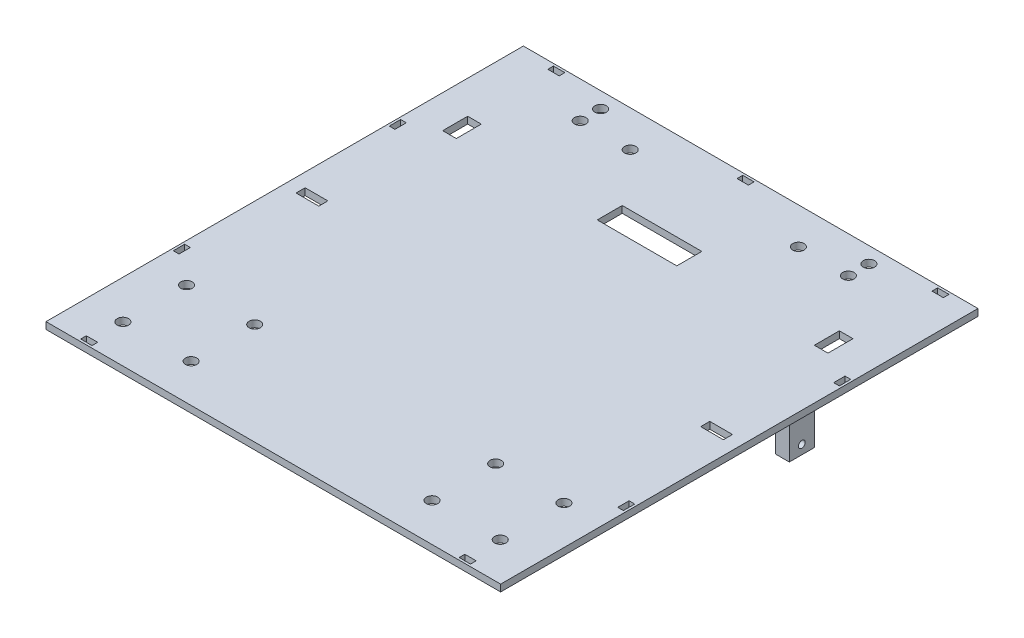
SolidWorks part; units mm, degrees
material "ABS"
ref_plane "Front Plane" through (0, 0, 0) normal (0, 0, 1) x (1, 0, 0)
ref_plane "Top Plane" through (0, 0, 0) normal (0, 1, 0) x (1, 0, 0)
ref_plane "Right Plane" through (0, 0, 0) normal (1, 0, 0) x (0, 0, -1)
sketch "Sketch1" plane through (0, 0, 0) normal (0, 1, 0) x (1, 0, 0)
  line L1 (100, 105) -> (-100, 105)
  line L2 (100, 105) -> (100, -105)
  line L3 (100, -105) -> (-100, -105)
  line L4 (-100, 105) -> (-100, -105)
  line L5 (100, 105) -> (-100, -105) construction
  line L6 (100, -105) -> (-100, 105) construction
  line L11 (94, 3) -> (84, 3)
  line L12 (94, 3) -> (94, -1)
  line L13 (94, -1) -> (84, -1)
  line L14 (84, 3) -> (84, -1)
  line L15 (94, 3) -> (84, -1) construction
  line L16 (94, -1) -> (84, 3) construction
  line L17 (-94, -1) -> (-84, -1)
  line L18 (-94, -1) -> (-94, 3)
  line L19 (-94, 3) -> (-84, 3)
  line L20 (-84, -1) -> (-84, 3)
  line L21 (-94, -1) -> (-84, 3) construction
  line L22 (-94, 3) -> (-84, -1) construction
  line L23 (-85.5, 38) -> (-79.5, 38)
  line L24 (-85.5, 38) -> (-85.5, 49)
  line L25 (-85.5, 49) -> (-79.5, 49)
  line L26 (-79.5, 38) -> (-79.5, 49)
  line L27 (-85.5, 38) -> (-79.5, 49) construction
  line L28 (-85.5, 49) -> (-79.5, 38) construction
  line L29 (78, 38) -> (84, 38)
  line L30 (78, 38) -> (78, 49)
  line L31 (78, 49) -> (84, 49)
  line L32 (84, 38) -> (84, 49)
  line L33 (78, 38) -> (84, 49) construction
  line L34 (78, 49) -> (84, 38) construction
  line L35 (85.75, -104) -> (80.75, -104)
  line L36 (85.75, -104) -> (85.75, -101.5)
  line L37 (85.75, -101.5) -> (80.75, -101.5)
  line L38 (80.75, -104) -> (80.75, -101.5)
  line L39 (85.75, -104) -> (80.75, -101.5) construction
  line L40 (85.75, -101.5) -> (80.75, -104) construction
  line L41 (-2.5, 101.5) -> (2.5, 101.5)
  line L42 (-2.5, 101.5) -> (-2.5, 104)
  line L43 (-2.5, 104) -> (2.5, 104)
  line L44 (2.5, 101.5) -> (2.5, 104)
  line L45 (-2.5, 101.5) -> (2.5, 104) construction
  line L46 (-2.5, 104) -> (2.5, 101.5) construction
  line L47 (-85.75, -104) -> (-80.75, -104)
  line L48 (-85.75, -104) -> (-85.75, -101.5)
  line L49 (-85.75, -101.5) -> (-80.75, -101.5)
  line L50 (-80.75, -104) -> (-80.75, -101.5)
  line L51 (-85.75, -104) -> (-80.75, -101.5) construction
  line L52 (-85.75, -101.5) -> (-80.75, -104) construction
  line L53 (-80.75, 104) -> (-85.75, 104)
  line L54 (-80.75, 104) -> (-80.75, 101.5)
  line L55 (-80.75, 101.5) -> (-85.75, 101.5)
  line L56 (-85.75, 104) -> (-85.75, 101.5)
  line L57 (-80.75, 104) -> (-85.75, 101.5) construction
  line L58 (-80.75, 101.5) -> (-85.75, 104) construction
  line L59 (83.25, 101.5) -> (88.25, 101.5)
  line L60 (83.25, 101.5) -> (83.25, 104)
  line L61 (83.25, 104) -> (88.25, 104)
  line L62 (88.25, 101.5) -> (88.25, 104)
  line L63 (83.25, 101.5) -> (88.25, 104) construction
  line L64 (83.25, 104) -> (88.25, 101.5) construction
  line L65 (99, -45) -> (96.5, -45)
  line L66 (99, -45) -> (99, -50)
  line L67 (99, -50) -> (96.5, -50)
  line L68 (96.5, -45) -> (96.5, -50)
  line L69 (99, -45) -> (96.5, -50) construction
  line L70 (99, -50) -> (96.5, -45) construction
  line L71 (99, 50) -> (96.5, 50)
  line L72 (99, 50) -> (99, 45)
  line L73 (99, 45) -> (96.5, 45)
  line L74 (96.5, 50) -> (96.5, 45)
  line L75 (99, 50) -> (96.5, 45) construction
  line L76 (99, 45) -> (96.5, 50) construction
  line L77 (-99, -45) -> (-96.5, -45)
  line L78 (-99, -45) -> (-99, -50)
  line L79 (-99, -50) -> (-96.5, -50)
  line L80 (-96.5, -45) -> (-96.5, -50)
  line L81 (-99, -45) -> (-96.5, -50) construction
  line L82 (-99, -50) -> (-96.5, -45) construction
  line L83 (-99, 45) -> (-96.5, 45)
  line L84 (-99, 45) -> (-99, 50)
  line L85 (-99, 50) -> (-96.5, 50)
  line L86 (-96.5, 45) -> (-96.5, 50)
  line L87 (-99, 45) -> (-96.5, 50) construction
  line L88 (-99, 50) -> (-96.5, 45) construction
  line L89 (84, 55) -> (78, 55)
  line L90 (84, 55) -> (84, 66)
  line L91 (84, 66) -> (78, 66)
  line L92 (78, 55) -> (78, 66)
  line L93 (-79.5, 55) -> (-85.5, 55)
  line L94 (-79.5, 55) -> (-79.5, 66)
  line L95 (-79.5, 66) -> (-85.5, 66)
  line L96 (-85.5, 55) -> (-85.5, 66)
  line L97 (-17.5, 66) -> (17.5, 66)
  line L98 (-17.5, 66) -> (-17.5, 55)
  line L99 (-17.5, 55) -> (17.5, 55)
  line L100 (17.5, 66) -> (17.5, 55)
  circle A0 centre (-59, 98) radius 2.5
  circle A1 centre (-59, 89) radius 2.5
  circle A2 centre (-37, 89) radius 2.5
  circle A3 centre (59, 98) radius 2.5
  circle A4 centre (59, 89) radius 2.5
  circle A5 centre (37, 89) radius 2.5
  circle A6 centre (83, -88.1753) radius 2.5
  circle A7 centre (83, -60.1753) radius 2.4959
  circle A8 centre (53, -88.1753) radius 2.5
  circle A9 centre (53, -60.1753) radius 2.5
  circle A10 centre (-83, -88.1753) radius 2.5
  circle A11 centre (-53, -88.1753) radius 2.5
  circle A12 centre (-53, -60.1753) radius 2.5
  circle A13 centre (-83, -60.1753) radius 2.5
  point P0 (0, 0)
  point P6 (89, 1)
  point P23 (-89, 1)
  point P28 (-82.5, 43.5)
  point P33 (81, 43.5)
  point P38 (83.25, -102.75)
  point P43 (0, 102.75)
  point P48 (-83.25, -102.75)
  point P53 (-83.25, 102.75)
  point P58 (85.75, 102.75)
  point P59 (97.75, -47.5)
  point P68 (97.75, -45)
  point P69 (97.75, 47.5)
  point P74 (-97.75, -47.5)
  point P79 (-97.75, 47.5)
  dimension "D7" = 16
  dimension "D8" = 63
  dimension "D9" = 16
  dimension "D11" = 7
  dimension "D13" = 41
  dimension "D15" = 63
  dimension "D17" = 10
  dimension "D79" = 28
  dimension "D80" = 30
  dimension "D82" = 28
  dimension "D83" = 30
  dimension "D1" = 200
  dimension "D2" = 210
  dimension "D3" = 41
  dimension "D4" = 41
  dimension "D5" = 7
  dimension "D6" = 104
  dimension "D10" = 16
  dimension "D12" = 16
  dimension "D14" = 41
  dimension "D16" = 6
  dimension "D18" = 4
  dimension "D19" = 104
  dimension "D20" = 6
  dimension "D21" = 4
  dimension "D22" = 10
  dimension "D23" = 56
  dimension "D24" = 14.5
  dimension "D25" = 11
  dimension "D26" = 6
  dimension "D27" = 56
  dimension "D28" = 6
  dimension "D29" = 11
  dimension "D30" = 16
  dimension "D31" = 14.25
  dimension "D32" = 1
  dimension "D33" = 5
  dimension "D34" = 2.5
  dimension "D35" = 1
  dimension "D36" = 100
  dimension "D37" = 5
  dimension "D38" = 2.5
  dimension "D39" = 1
  dimension "D40" = 14.25
  dimension "D41" = 5
  dimension "D42" = 2.5
  dimension "D43" = 14.25
  dimension "D44" = 1
  dimension "D45" = 5
  dimension "D46" = 2.5
  dimension "D47" = 14.25
  dimension "D48" = 1
  dimension "D49" = 5
  dimension "D50" = 2.5
  dimension "D51" = 1
  dimension "D52" = 5
  dimension "D53" = 2.5
  dimension "D54" = 55
  dimension "D55" = 55
  dimension "D56" = 1
  dimension "D57" = 5
  dimension "D58" = 2.5
  dimension "D59" = 1
  dimension "D60" = 55
  dimension "D61" = 2.5
  dimension "D62" = 5
  dimension "D63" = 55
  dimension "D64" = 1
  dimension "D65" = 2.5
  dimension "D66" = 5
  dimension "D67" = 16
  dimension "D68" = 11
  dimension "D69" = 6
  dimension "D70" = 39
  dimension "D71" = 14.5
  dimension "D72" = 39
  dimension "D73" = 11
  dimension "D74" = 6
  dimension "D75" = 39
  dimension "D76" = 82.5
  dimension "D77" = 35
  dimension "D78" = 11
  dimension "D81" = 17
  dimension "D84" = 17
extrude "MainBody" add sketch "Sketch1" along normal blind 1
extrude "SayapRoda" add sketch "Sketch1<4>" against normal blind 30 and the other way blind 3 separate body contours L23 L26 L25 L24 | L29 L32 L31 L30 region at (-82.5, 0, -43.5) region at (81, 0, -43.5)
sketch "Sketch1<4>" plane through (0, 0, 0) normal (0, 1, 0) x (1, 0, 0) same geometry as "Sketch1"
hole_wizard "Hole1" positions "3DSketch2" profile "Sketch9" legacy end condition through all
sketch3d "3DSketch2"
  line L0 (84, 3, -49) -> (84, -30, -49) construction
  line L1 (84, -30, -38) -> (84, -30, -49) construction
  point P0 (84, -26, -43.5)
  point P2 (84, -9.0002, -43.4154)
  point P4 (84, -7.7287, -43.5)
  point P6 (84, -6.2408, -43.5)
  point P8 (84, -4.8783, -43.5)
  dimension "D1" = 17
  dimension "D2" = 5.5
  dimension "D3" = 5.5
  dimension "D4" = 5.5
  dimension "D5" = 5.5
  dimension "D6" = 4
sketch "Sketch9" plane through (84, -26, -43.5) normal (0, 1, 0) x (0, 0, -1)
  line L0 (0, 0) -> (0, 184)
  line L1 (0, 184) -> (1.5, 184)
  line L2 (1.5, 184) -> (1.5, 0)
  line L3 (1.5, 0) -> (0, 0)
  line L4 (0, 110) -> (0, -10) construction
  dimension "Diameter" = 3
  dimension "Depth" = 184
extrude "Boss-Extrude1" add sketch "Sketch1<7>" along normal blind 3
sketch "Sketch1<7>" plane through (0, 0, 0) normal (0, 1, 0) x (1, 0, 0) same geometry as "Sketch1"
